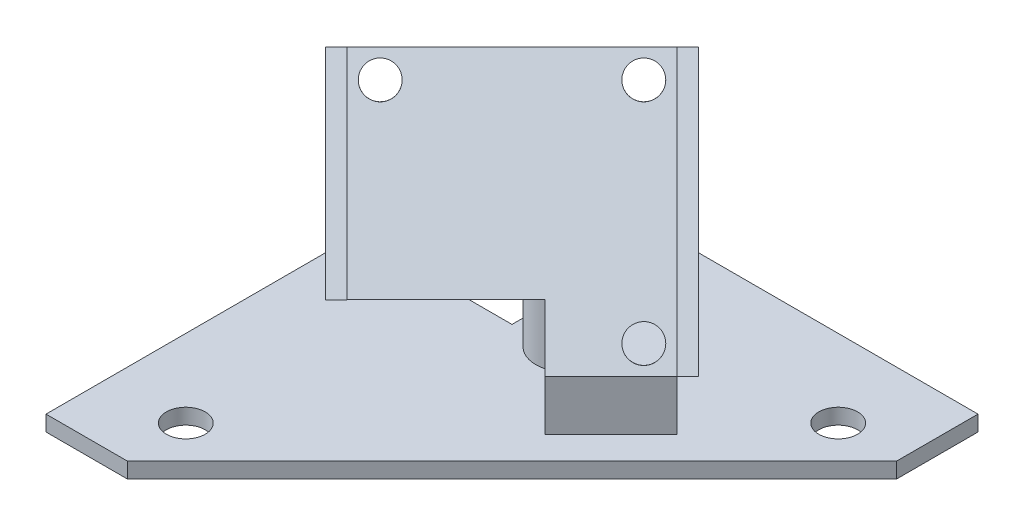
SolidWorks part; units mm, degrees
ref_plane "Front" through (0, 0, 0) normal (0, 0, 1) x (1, 0, 0)
ref_plane "Top" through (0, 0, 0) normal (0, 1, 0) x (1, 0, 0)
ref_plane "Right" through (0, 0, 0) normal (1, 0, 0) x (0, 0, -1)
sketch "草图1" plane through (0, 0, 0) normal (0, 1, 0) x (1, 0, 0)
  line L0 (87.1745, 16.672) -> (1.4976, -69.0049)
  line L1 (0, 0) -> (60, 0)
  line L2 (0, 0) -> (0, -60)
  line L3 (0, -60) -> (60, -60)
  line L4 (60, 0) -> (60, -60)
  line L5 (0, 0) -> (20, 0)
  line L6 (0, 0) -> (0, -20)
  line L7 (0, -20) -> (20, -20)
  line L8 (20, 0) -> (20, -20)
  circle A0 centre (10, -52) radius 2.5
  circle A1 centre (52, -10) radius 2.5
  dimension "D5" = 5
  dimension "D8" = 5
  dimension "D1" = 60
  dimension "D2" = 60
  dimension "D3" = 20
  dimension "D4" = 20
  dimension "D6" = 10
  dimension "D7" = 8
  dimension "D9" = 10
  dimension "D10" = 8
  dimension "D11" = 35
extrude "凸台-拉伸1" add sketch "草图1" along normal blind 2 contours L1 L8 L7 L2 L3 L4 region at (25.5687, 0, 25.5687)
ref_plane "基准面1" through (24.3184, 24.0811, 24.3184) normal (0.5792, 0.5736, 0.5792) x (-0.7071, 0, 0.7071)
sketch "草图2" plane through (24.3184, 24.0811, 24.3184) normal (0.5792, 0.5736, 0.5792) x (-0.7071, 0, 0.7071)
  line L0 (20.7547, -10.214) -> (-21.3736, -10.214) construction
  line L1 (-15, 16.786) -> (15, 16.786)
  line L2 (-15, 16.786) -> (-15, -13.214)
  line L3 (-15, -13.214) -> (15, -13.214)
  line L4 (15, 16.786) -> (15, -13.214)
  line L5 (-15, 16.786) -> (15, -13.214) construction
  line L6 (-15, -13.214) -> (15, 16.786) construction
  line L7 (0, -2.8326) -> (0, 36.0846) construction
  line L8 (27.4605, 1.786) -> (-33.4746, 1.786) construction
  line L10 (15, 16.786) -> (-3, 16.786)
  line L11 (15, 16.786) -> (15, 9.786)
  line L12 (15, 9.786) -> (-3, 9.786)
  line L13 (-3, 16.786) -> (-3, 9.786)
  circle A0 centre (12, -10.214) radius 2
  circle A1 centre (-12, -10.214) radius 2
  circle A2 centre (-12, 13.786) radius 2
  circle A3 centre (12, 13.786) radius 2
  point P0 (0, 1.786)
  dimension "D4" = 4
  dimension "D1" = 30
  dimension "D2" = 30
  dimension "D3" = 12
  dimension "D5" = 12
  dimension "D6" = 7
  dimension "D7" = 18
extrude "凸台-拉伸3" add sketch "草图2" along normal blind 2 separate body contours L13 L1 L2 L3 L4 L12 A2 A0 A1 region at (24.9089, 24.0624, 23.7465)
sketch "草图4" plane through (0, 2, 0) normal (0, 1, 0) x (1, 0, 0)
  line L12 (30.4088, -40.3082) -> (33.2478, -43.1473)
  line L13 (17.6808, -53.0362) -> (30.4088, -40.3082)
  line L14 (-5.7896, -29.5657) -> (17.6808, -53.0362)
  line L15 (29.5657, 5.7896) -> (-5.7896, -29.5657)
  line L16 (55.8752, -20.5199) -> (29.5657, 5.7896)
  line L17 (33.2478, -43.1473) -> (55.8752, -20.5199)
  line L18 (30.4088, -40.3082) -> (33.2478, -43.1473)
  line L19 (17.6808, -53.0362) -> (30.4088, -40.3082)
  line L20 (-5.7896, -29.5657) -> (17.6808, -53.0362)
  line L21 (29.5657, 5.7896) -> (-5.7896, -29.5657)
  line L22 (55.8752, -20.5199) -> (29.5657, 5.7896)
  line L23 (33.2478, -43.1473) -> (55.8752, -20.5199)
  circle A0 centre (26.0302, -18.9591) radius 4
  dimension "D2" = 8
  dimension "D3" = 15
  dimension "D4" = 20
  dimension "D1" = 10
extrude "凸台-拉伸4" add sketch "草图4" along normal up to surface (21.7252 mm away) contours A0 region at (26.0302, 2, 18.9591) up to face at (39.8092, 12.7883, 20.0103)
sketch "草图5" plane through (0, 2, 0) normal (0, 1, 0) x (1, 0, 0)
  line L4 (41.7331, -20.5199) -> (33.2478, -29.0052)
  line L5 (42.8915, -21.6783) -> (41.7331, -20.5199)
  line L6 (34.4063, -30.1636) -> (42.8915, -21.6783)
  line L7 (60, 0) -> (20, 0)
  line L8 (20, 0) -> (20, -20)
  line L9 (20, -20) -> (0, -20)
  line L10 (0, -20) -> (0, -60)
  line L11 (0, -60) -> (10.5025, -60)
  line L12 (10.5025, -60) -> (60, -10.5025)
  line L13 (60, -10.5025) -> (60, 0)
  line L14 (60, 0) -> (20, 0)
  line L15 (20, 0) -> (20, -20)
  line L16 (20, -20) -> (0, -20)
  line L17 (0, -20) -> (0, -60)
  line L18 (0, -60) -> (10.5025, -60)
  line L19 (10.5025, -60) -> (60, -10.5025)
  line L20 (60, -10.5025) -> (60, 0)
  line L21 (33.2478, -29.0052) -> (34.4063, -30.1636)
  line L22 (41.7331, -20.5199) -> (33.2478, -29.0052)
  line L23 (42.8915, -21.6783) -> (41.7331, -20.5199)
  line L24 (34.4063, -30.1636) -> (42.8915, -21.6783)
  line L25 (33.2478, -29.0052) -> (34.4063, -30.1636)
  dimension "D1" = 0
  dimension "D2" = 0
extrude "凸台-拉伸5" add sketch "草图5" along normal up to next contours L22 L25 L24 L23 region at (38.0697, 2, 25.3418)
sketch "草图6" plane through (25.4769, 25.2283, 25.4769) normal (0.5792, 0.5736, 0.5792) x (0.4511, 0.3663, -0.8138)
  line L0 (-7.5069, 18.5271) -> (-17.7929, -2.0447)
  line L1 (-7.5069, 18.5271) -> (-9.2958, 19.4216)
  line L2 (-17.7929, -2.0447) -> (-19.5817, -1.1503)
  line L3 (-9.2958, 19.4216) -> (-19.5817, -1.1503)
  line L4 (19.3259, 5.1107) -> (5.9095, -21.7221)
  line L5 (19.3259, 5.1107) -> (21.1147, 4.2163)
  line L6 (5.9095, -21.7221) -> (7.6983, -22.6165)
  line L7 (21.1147, 4.2163) -> (7.6983, -22.6165)
  dimension "D1" = 2
  dimension "D2" = 2
extrude "凸台-拉伸6" add sketch "草图6" against normal up to surface (2 mm away) and the other way blind 3 up to face at (28.8586, 22.0521, 21.7875)
sketch "草图7" plane through (0, 2, 0) normal (0, 1, 0) x (1, 0, 0)
  line L7 (60, 0) -> (20, 0)
  line L8 (20, 0) -> (20, -20)
  line L9 (20, -20) -> (0, -20)
  line L10 (0, -20) -> (0, -60)
  line L11 (0, -60) -> (10.5025, -60)
  line L12 (10.5025, -60) -> (60, -10.5025)
  line L13 (60, -10.5025) -> (60, 0)
  line L14 (60, 0) -> (20, 0)
  line L15 (20, 0) -> (20, -20)
  line L16 (20, -20) -> (0, -20)
  line L17 (0, -20) -> (0, -60)
  line L18 (0, -60) -> (10.5025, -60)
  line L19 (10.5025, -60) -> (60, -10.5025)
  line L20 (60, -10.5025) -> (60, 0)
  circle A0 centre (10, -52) radius 2.5 construction
  circle A1 centre (52, -10) radius 2.5 construction
  circle A2 centre (10, -52) radius 2.5
  circle A3 centre (52, -10) radius 2.5
  dimension "D1" = 0
extrude "凸台-拉伸8" add sketch "草图7" along normal blind 3
sketch "草图10" plane through (0, 0, 0) normal (0, -1, 0) x (1, 0, 0)
  line L7 (20, 0) -> (60, 0)
  line L8 (60, 0) -> (60, 10.5025)
  line L9 (60, 10.5025) -> (10.5025, 60)
  line L10 (10.5025, 60) -> (0, 60)
  line L11 (0, 60) -> (0, 20)
  line L12 (0, 20) -> (20, 20)
  line L13 (20, 20) -> (20, 0)
  line L14 (20, 0) -> (60, 0)
  line L15 (60, 0) -> (60, 10.5025)
  line L16 (60, 10.5025) -> (10.5025, 60)
  line L17 (10.5025, 60) -> (0, 60)
  line L18 (0, 60) -> (0, 20)
  line L19 (0, 20) -> (20, 20)
  line L20 (20, 20) -> (20, 0)
  dimension "D1" = 0
extrude "切除-拉伸1" cut sketch "草图10" against normal blind 3
